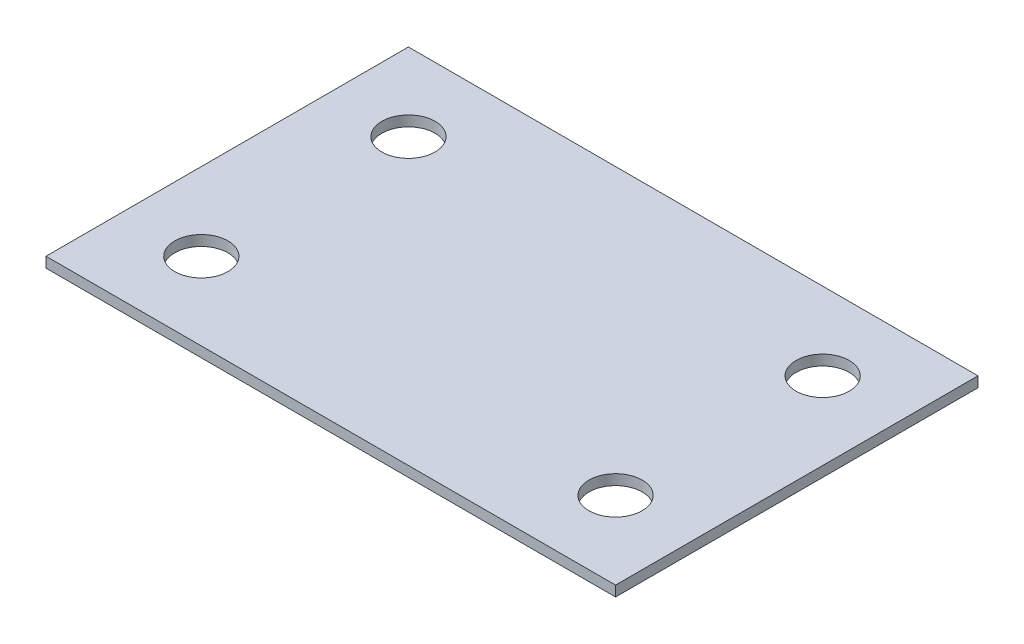
SolidWorks part; units mm, degrees
ref_plane "Front Plane" through (0, 0, 0) normal (0, 0, 1) x (1, 0, 0)
ref_plane "Top Plane" through (0, 0, 0) normal (0, 1, 0) x (1, 0, 0)
ref_plane "Right Plane" through (0, 0, 0) normal (1, 0, 0) x (0, 0, -1)
sketch "Sketch1" plane through (0, 0, 0) normal (0, 1, 0) x (1, 0, 0)
  line L0 (9.525, 34.925) -> (0, 34.925) construction
  line L1 (0, 0) -> (69.85, 0)
  line L2 (0, 0) -> (0, 44.45)
  line L3 (0, 44.45) -> (69.85, 44.45)
  line L4 (69.85, 0) -> (69.85, 44.45)
  line L5 (9.525, 34.925) -> (60.325, 34.925) construction
  line L6 (9.525, 34.925) -> (9.525, 9.525) construction
  line L7 (9.525, 9.525) -> (60.325, 9.525) construction
  line L8 (60.325, 34.925) -> (60.325, 9.525) construction
  line L9 (9.525, 34.925) -> (9.525, 44.45) construction
  circle A0 centre (9.525, 34.925) radius 3.2639
  circle A1 centre (60.325, 34.925) radius 3.2639
  circle A2 centre (9.525, 9.525) radius 3.2639
  circle A3 centre (60.325, 9.525) radius 3.2639
  point P13 (34.925, 34.925)
  point P14 (34.925, 44.45)
  dimension "D5" = 6.5278
  dimension "D1" = 69.85
  dimension "D2" = 44.45
  dimension "D3" = 50.8
  dimension "D4" = 25.4
extrude "Boss-Extrude1" add sketch "Sketch1" along normal blind 1.27
